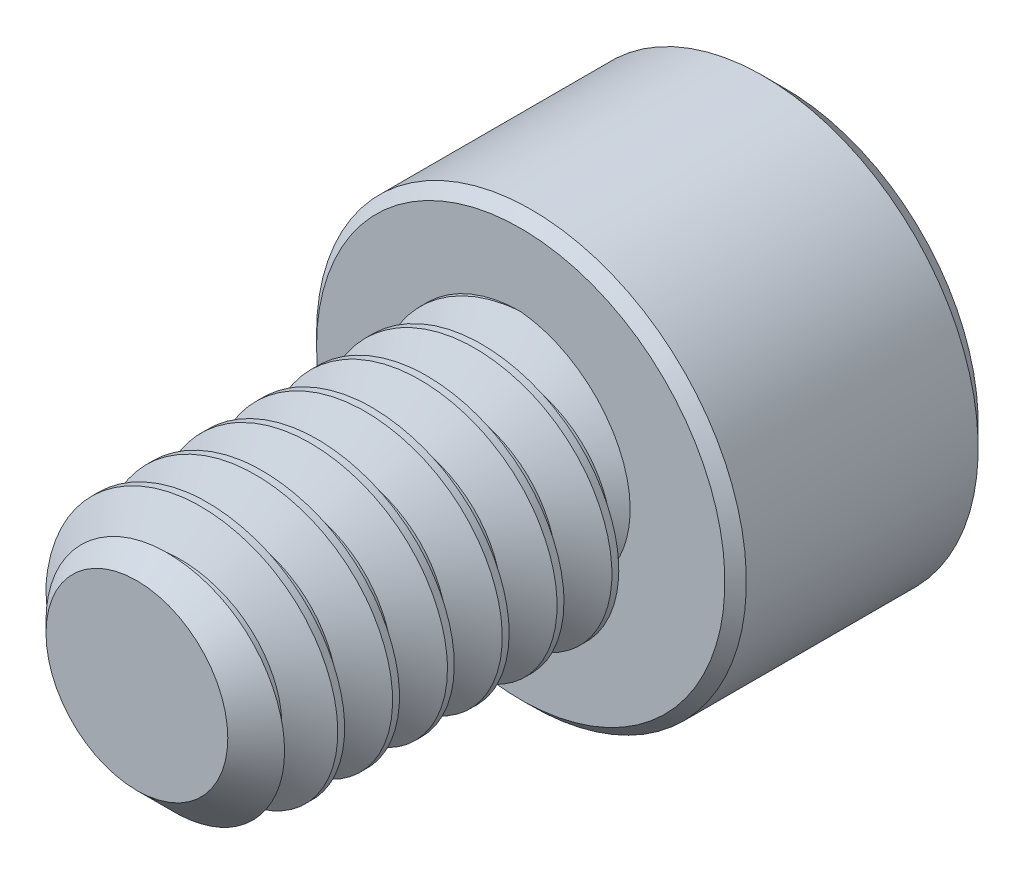
SolidWorks part; units mm, degrees
ref_plane "Front Plane" through (0, 0, 0) normal (0, 0, 1) x (1, 0, 0)
ref_plane "Top Plane" through (0, 0, 0) normal (0, 1, 0) x (1, 0, 0)
ref_plane "Right Plane" through (0, 0, 0) normal (1, 0, 0) x (0, 0, -1)
sketch "Sketch0" plane through (0, 0, 0) normal (1, 0, 0) x (0, 0, -1)
  line L0 (0, 0) -> (3.175, 0) construction
  point P2 (5.3594, 0)
  point P4 (0, 0)
  dimension "D1" = 3.175
  dimension "D2" = 2.1844
  dimension "Min Thread" = 0
sketch "Sketch1" plane through (0, 0, 0) normal (0, 0, 1) x (1, 0, 0)
  circle A0 centre (0, 0) radius 1.0922
  dimension "OD" = 2.1844
extrude "Extrude1" add sketch "Sketch1" against normal blind 3.175
sketch "Sketch2" plane through (0, 0, 0) normal (0, 0, 1) x (1, 0, 0)
  circle A0 centre (0, 0) radius 1.0922 construction
  circle A1 centre (0, 0) radius 1.0922
curve "Helix/Spiral1" pitch 0.4536 height 3.6286 radius 1.0922 centre (0, 0, 0) axis (0, 0, -1) start towards (0, 1, 0) parameters "pitch"=0.4536
chamfer "Chamfer3" distance 0.3402 angle 45 1 edges at (1.0922, 0, 0)
sketch "Sketch3" plane through (0, 0, 0) normal (1, 0, 0) x (0, 0, -1)
  line L0 (-0.3969, 1.0922) -> (-0.2268, 0.7976)
  line L1 (-0.2268, 0.7976) -> (-0.1701, 0.7976)
  line L2 (-0.1701, 0.7976) -> (0, 1.0922)
  line L3 (-0.3969, 1.0922) -> (0, 1.0922)
  line L4 (-0.1984, 1.0922) -> (-0.1984, 0.7976) construction
  line L5 (-0.3118, 0.9449) -> (-0.085, 0.9449) construction
  line L6 (0, 1.0922) -> (0, -1.0922) construction
  dimension "D1" = 0.0567
  dimension "D2" = 0.2268
  dimension "D3" = 60
sweep "Cut-Sweep1" cut profiles "Sketch3" path "Helix/Spiral1" align with end faces yes
sketch "Sketch5" plane through (0, 0, 0) normal (1, 0, 0) x (0, 0, -1)
  line L0 (3.175, -0.8061) -> (3.175, 0.7793) construction
  line L1 (3.175, 1.0922) -> (0, 1.0922)
  line L2 (3.175, 1.0922) -> (3.175, 0)
  line L3 (3.175, 0) -> (-0.3975, 0)
  line L4 (0, 0) -> (3.175, 0) construction
  line L5 (0, 1.0922) -> (-0.3975, 0)
  line L6 (0, 0) -> (5.715, 0) construction
  dimension "D1" = 70
  dimension "D3" = 2.54
revolve "partially thread" [suppressed] add sketch "Sketch5" angle 360 about L6
sketch "Sketch6" plane through (0, 0, -3.175) normal (0, 0, -1) x (-1, 0, 0)
  circle A0 centre (0, 0) radius 1.778
  dimension "head dia" = 3.556
extrude "Extrude2" add sketch "Sketch6" along normal blind 2.1844
sketch "Sketch7" plane through (0, 0, -5.3594) normal (0, 0, -1) x (-1, 0, 0)
  line L1 (0, 1.1457) -> (-0.9922, 0.5728)
  line L2 (-0.9922, 0.5728) -> (-0.9922, -0.5728)
  line L3 (-0.9922, -0.5728) -> (0, -1.1457)
  line L4 (0, -1.1457) -> (0.9922, -0.5728)
  line L5 (0.9922, -0.5728) -> (0.9922, 0.5728)
  line L6 (0.9922, 0.5728) -> (0, 1.1457)
  circle A0 centre (0, 0) radius 0.9922 construction
  dimension "hex dia" = 1.9844
extrude "Cut-Extrude1" cut sketch "Sketch7" against normal blind 1.4883
sketch "Sketch8" plane through (0, 0, -5.3594) normal (0, 0, -1) x (-1, 0, 0)
  circle A0 centre (0, 0) radius 1.1457
extrude "Cut-Extrude2" cut sketch "Sketch8" against normal through all draft 45
chamfer "Chamfer1" distance 0.1778 angle 45 1 edges at (-1.778, 0, -5.3594)
chamfer "Chamfer2" distance 0.0889 angle 45 1 edges at (-1.778, 0, -3.175)
sketch "Sketch9" plane through (0, 0, 0) normal (1, 0, 0) x (0, 0, -1)
  line L0 (0, 1.0922) -> (0, -1.0922) construction
  line L1 (1.5875, 1.0922) -> (1.5875, -1.0922) construction
  line L2 (5.3594, 1.778) -> (5.3594, -1.778) construction
  line L3 (3.175, 1.778) -> (3.175, -1.778) construction
  line L4 (3.175, 1.6891) -> (3.175, -1.6891) construction
  line L5 (5.3594, -1.6002) -> (5.3594, 1.6002) construction
  line L6 (3.175, -1.778) -> (3.175, 1.778) construction
  line L7 (0, 0.752) -> (0, -0.752) construction
  line L8 (-0.3969, 1.0922) -> (0, 1.0922) construction
  line L9 (1.5875, 0) -> (0, 0) construction
  dimension "D1" = 1.5875
equation "\"D3@Helix/Spiral1\" = \"screw length@Extrude1\"+\"pitch@Helix/Spiral1\""
equation "\"D1@Sketch3\" = \"pitch@Helix/Spiral1\"*.125"
equation "\"D2@Sketch3\" = \"pitch@Helix/Spiral1\"*.5"
equation "\"D1@Cut-Extrude1\" = \"hex dia@Sketch7\"*.75"
equation "\"D1@Chamfer1\" = \"head dia@Sketch6\"*.05"
equation "\"D1@Sketch9\" = \"pitch@Helix/Spiral1\"*3.50"
equation "\"D1@Chamfer2\" = \"D1@Chamfer1\"/2"
equation "\"D1@Chamfer3\" = \"pitch@Helix/Spiral1\"*.750"
equation "\"D1@Sketch0\" = \"screw length@Extrude1\""
equation "\"D2@Sketch0\" = \"head depth@Extrude2\""
